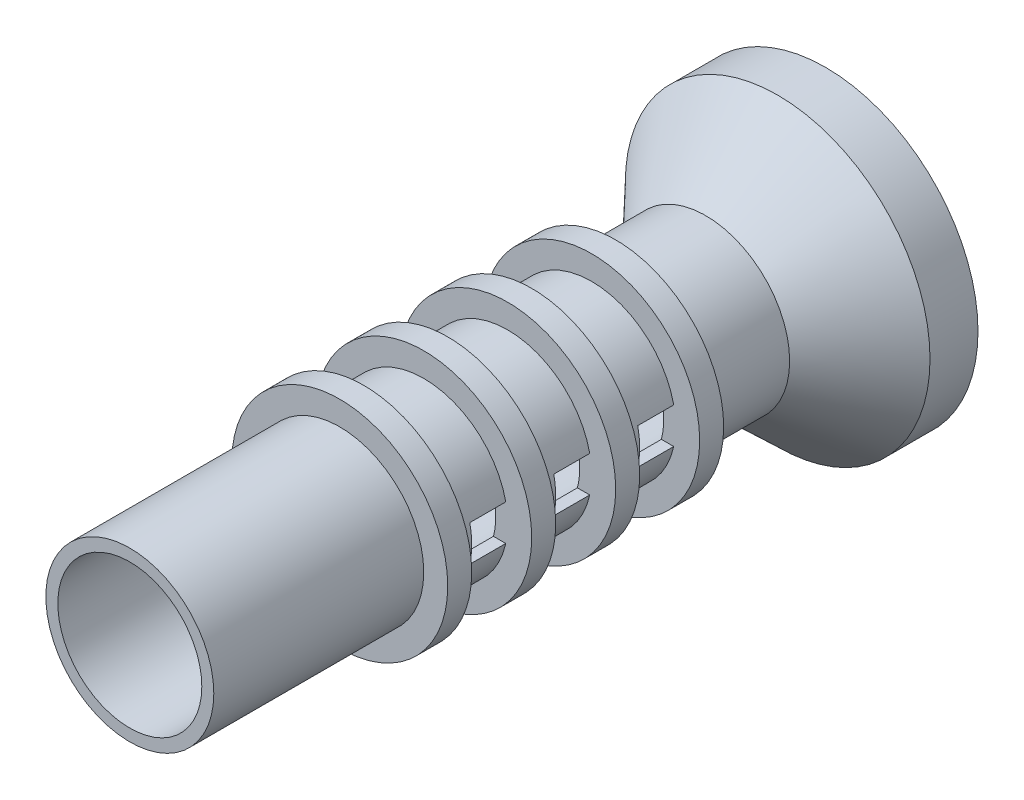
SolidWorks part; units mm, degrees
material "ABS"
ref_plane "正面" through (0, 0, 0) normal (0, 0, 1) x (1, 0, 0)
ref_plane "平面" through (0, 0, 0) normal (0, 1, 0) x (1, 0, 0)
ref_plane "右側面" through (0, 0, 0) normal (1, 0, 0) x (0, 0, -1)
sketch "ｽｹｯﾁ1" plane through (0, 0, 0) normal (0, 0, 1) x (1, 0, 0)
  circle A0 centre (0, 0) radius 3.5 construction
  circle A1 centre (0, 0) radius 6.35
  dimension "D1" = 7
  dimension "D2" = 12.7
ref_plane "平面1" through (0, 0, 5) normal (0, 0, 1) x (1, 0, 0)
sketch "ｽｹｯﾁ2" plane through (0, 0, 5) normal (0, 0, 1) x (1, 0, 0)
  circle A0 centre (0, 0) radius 3.5 construction
  circle A1 centre (0, 0) radius 3.5
ref_plane "平面2" through (0, 0, 29) normal (0, 0, 1) x (1, 0, 0)
ref_plane "平面3" through (0, 0, 24) normal (0, 0, 1) x (1, 0, 0)
sketch "ｽｹｯﾁ5" plane through (0, 0, 29) normal (0, 0, 1) x (1, 0, 0)
  circle A0 centre (0, 0) radius 6.35 construction
  circle A1 centre (0, 0) radius 6.35 construction
  circle A2 centre (0, 0) radius 3.5
  dimension "D1" = 7
extrude "ﾎﾞｽ - 押し出し3" add sketch "ｽｹｯﾁ2" along normal up to surface (19 mm away) contours A1 up to plane "平面3"
extrude "ﾎﾞｽ - 押し出し4" add sketch "ｽｹｯﾁ1" along normal blind 2 separate body
extrude "ﾎﾞｽ - 押し出し5" add sketch "ｽｹｯﾁ5" against normal blind 2
loft "ﾛﾌﾄ1" add section face at (6.35, 0, 2) section face at (3.5, 0, 5) connector at (-0.1759, 6.3476, 2) connector at (-0.0742, 3.4992, 5)
loft "ﾛﾌﾄ2" add section face at (3.5, 0, 24) section face at (3.5, 0, 27) connector at (-0.0749, 3.4992, 24) connector at (-0.0751, 3.4992, 27)
ref_plane "平面5" through (0, 0, 14.5) normal (0, 0, 1) x (1, 0, 0)
ref_plane "平面6" through (0, 0, 15.75) normal (0, 0, 1) x (1, 0, 0)
sketch "ｽｹｯﾁ9" plane through (0, 0, 15.75) normal (0, 0, 1) x (1, 0, 0)
  circle A0 centre (0, 0) radius 4.5
  dimension "D1" = 9
extrude "ﾎﾞｽ - 押し出し6" add sketch "ｽｹｯﾁ9" along normal blind 1
ref_plane "平面7" through (0, 0, 19.25) normal (0, 0, 1) x (1, 0, 0)
sketch "ｽｹｯﾁ10" plane through (0, 0, 19.25) normal (0, 0, 1) x (1, 0, 0)
  circle A1 centre (0, 0) radius 4.5
  circle A2 centre (0, 0) radius 4.5
  dimension "D1" = 0
extrude "ﾎﾞｽ - 押し出し7" add sketch "ｽｹｯﾁ10" along normal blind 1
mirror "ﾐﾗｰ3" about plane through (0, 0, 14.5) normal (0, 0, 1) of "ﾎﾞｽ - 押し出し7", "ﾎﾞｽ - 押し出し6"
sketch "ｽｹｯﾁ6" plane through (0, 0, 0) normal (0, 0, -1) x (-1, 0, 0)
  circle A0 centre (0, 0) radius 2.9
  dimension "D1" = 5.8
extrude "ｶｯﾄ - 押し出し1" cut sketch "ｽｹｯﾁ6" against normal blind 3
sketch "ｽｹｯﾁ7" plane through (0, 0, 3) normal (0, 0, -1) x (-1, 0, 0)
  circle A0 centre (0, 0) radius 1.8
  dimension "D1" = 3.6
extrude "ｶｯﾄ - 押し出し2" cut sketch "ｽｹｯﾁ7" against normal through all
sketch "ｽｹｯﾁ8" plane through (0, 0, 29) normal (0, 0, 1) x (1, 0, 0)
  circle A0 centre (0, 0) radius 3
  dimension "D1" = 6
extrude "ｶｯﾄ - 押し出し3" cut sketch "ｽｹｯﾁ8" against normal offset from surface (23 mm away) 3 up to face at (-1.8, 0, 3)
ref_plane "平面9" through (3.5, 0, 0) normal (1, 0, 0) x (0, 0, -1)
sketch "ｽｹｯﾁ11" plane through (3.5, 0, 0) normal (1, 0, 0) x (0, 0, -1)
  line L0 (0, 0) -> (-29, 0) construction
  line L1 (-29, 6.9851) -> (-29, -6.9851) construction
  line L2 (-16.75, 3.5) -> (-16.75, -3.5) construction
  line L3 (-18.25, 0.75) -> (-16.75, 0.75)
  line L4 (-18.25, 0.75) -> (-18.25, -0.75)
  line L5 (-18.25, -0.75) -> (-16.75, -0.75)
  line L6 (-16.75, 0.75) -> (-16.75, -0.75)
  line L7 (-18.25, 0.75) -> (-16.75, -0.75) construction
  line L8 (-18.25, -0.75) -> (-16.75, 0.75) construction
  line L9 (-13.25, 4.5) -> (-13.25, -4.5) construction
  line L10 (-14.75, 0.75) -> (-13.25, 0.75)
  line L11 (-14.75, 0.75) -> (-14.75, -0.75)
  line L12 (-14.75, -0.75) -> (-13.25, -0.75)
  line L13 (-13.25, 0.75) -> (-13.25, -0.75)
  line L14 (-14.75, 0.75) -> (-13.25, -0.75) construction
  line L15 (-14.75, -0.75) -> (-13.25, 0.75) construction
  line L16 (-9.75, 3.5) -> (-9.75, -3.5) construction
  line L17 (-11.25, 0.75) -> (-9.75, 0.75)
  line L18 (-11.25, 0.75) -> (-11.25, -0.75)
  line L19 (-11.25, -0.75) -> (-9.75, -0.75)
  line L20 (-9.75, 0.75) -> (-9.75, -0.75)
  line L21 (-11.25, 0.75) -> (-9.75, -0.75) construction
  line L22 (-11.25, -0.75) -> (-9.75, 0.75) construction
  point P5 (-17.5, 0)
  point P12 (-14, 0)
  point P19 (-10.5, 0)
  dimension "D1" = 1.5
  dimension "D2" = 1.5
extrude "ｶｯﾄ - 押し出し4" cut sketch "ｽｹｯﾁ11" against normal up to next
sketch "ｽｹｯﾁ12" plane through (0, 0, 0) normal (0, 0, -1) x (-1, 0, 0)
  line L0 (0, 0) -> (0, 2.9) construction
  line L1 (0, 0) -> (0.3949, 2.873) construction
  line L2 (0, 0) -> (0.7824, 2.7925) construction
  line L3 (0, 0) -> (1.1554, 2.6599) construction
  line L4 (0, 0) -> (1.5068, 2.4778) construction
  line L5 (0, 0) -> (1.8302, 2.2496) construction
  line L6 (0, 0) -> (2.1194, 1.9794) construction
  line L7 (0, 0) -> (2.3692, 1.6724) construction
  line L8 (0, 0) -> (2.5749, 1.3342) construction
  line L9 (0, 0) -> (2.7326, 0.9712) construction
  line L10 (0, 0) -> (2.8393, 0.59) construction
  line L11 (0, 0) -> (2.8932, 0.1979) construction
  line L12 (0, 0) -> (2.8932, -0.1979) construction
  line L13 (0, 0) -> (2.8393, -0.59) construction
  line L14 (0, 0) -> (2.7326, -0.9712) construction
  line L15 (0, 0) -> (2.5749, -1.3342) construction
  line L16 (0, 0) -> (2.3692, -1.6724) construction
  line L17 (0, 0) -> (2.1194, -1.9794) construction
  line L18 (0, 0) -> (1.8302, -2.2496) construction
  line L19 (0, 0) -> (1.5068, -2.4778) construction
  line L20 (0, 0) -> (1.1554, -2.6599) construction
  line L21 (0, 0) -> (0.7824, -2.7925) construction
  line L22 (0, 0) -> (0.3949, -2.873) construction
  line L23 (0, 0) -> (0, -2.9) construction
  line L24 (0, 0) -> (-0.3949, -2.873) construction
  line L25 (0, 0) -> (-0.7824, -2.7925) construction
  line L26 (0, 0) -> (-1.1554, -2.6599) construction
  line L27 (0, 0) -> (-1.5068, -2.4778) construction
  line L28 (0, 0) -> (-1.8302, -2.2496) construction
  line L29 (0, 0) -> (-2.1194, -1.9794) construction
  line L30 (0, 0) -> (-2.3692, -1.6724) construction
  line L31 (0, 0) -> (-2.5749, -1.3342) construction
  line L32 (0, 0) -> (-2.7326, -0.9712) construction
  line L33 (0, 0) -> (-2.8393, -0.59) construction
  line L34 (0, 0) -> (-2.8932, -0.1979) construction
  line L35 (0, 0) -> (-2.8932, 0.1979) construction
  line L36 (0, 0) -> (-2.8393, 0.59) construction
  line L37 (0, 0) -> (-2.7326, 0.9712) construction
  line L38 (0, 0) -> (-2.5749, 1.3342) construction
  line L39 (0, 0) -> (-2.3692, 1.6724) construction
  line L40 (0, 0) -> (-2.1194, 1.9794) construction
  line L41 (0, 0) -> (-1.8302, 2.2496) construction
  line L42 (0, 0) -> (-1.5068, 2.4778) construction
  line L43 (0, 0) -> (-1.1554, 2.6599) construction
  line L44 (0, 0) -> (-0.7824, 2.7925) construction
  line L45 (0, 0) -> (-0.3949, 2.873) construction
  line L46 (0, 0) -> (0.2081, 3.0429) construction
  line L47 (0.2081, 3.0429) -> (-0.066, 2.8992)
  line L48 (-0.066, 2.8992) -> (0, 0) construction
  line L49 (0, 0) -> (0.4602, 2.8633) construction
  line L50 (0.4602, 2.8633) -> (0.2081, 3.0429)
  line L51 (1.0214, 2.8739) -> (0.7186, 2.8095)
  line L52 (1.2156, 2.6329) -> (1.0214, 2.8739)
  line L53 (1.7589, 2.4918) -> (1.45, 2.5115)
  line L54 (1.8809, 2.2073) -> (1.7589, 2.4918)
  line L55 (2.3659, 1.9248) -> (2.0738, 2.0271)
  line L56 (2.4067, 1.618) -> (2.3659, 1.9248)
  line L57 (2.7975, 1.2151) -> (2.5438, 1.3925)
  line L58 (2.754, 0.9087) -> (2.7975, 1.2151)
  line L59 (3.0216, 0.4153) -> (2.8252, 0.6545)
  line L60 (2.897, 0.132) -> (3.0216, 0.4153)
  line L61 (3.0216, -0.4153) -> (2.897, -0.132)
  line L62 (2.8252, -0.6545) -> (3.0216, -0.4153)
  line L63 (2.7975, -1.2151) -> (2.754, -0.9087)
  line L64 (2.5438, -1.3925) -> (2.7975, -1.2151)
  line L65 (2.3659, -1.9248) -> (2.4067, -1.618)
  line L66 (2.0738, -2.0271) -> (2.3659, -1.9248)
  line L67 (1.7589, -2.4918) -> (1.8809, -2.2073)
  line L68 (1.45, -2.5115) -> (1.7589, -2.4918)
  line L69 (1.0214, -2.8739) -> (1.2156, -2.6329)
  line L70 (0.7186, -2.8095) -> (1.0214, -2.8739)
  line L71 (0.2081, -3.0429) -> (0.4602, -2.8633)
  line L72 (-0.066, -2.8992) -> (0.2081, -3.0429)
  line L73 (-0.6205, -2.9862) -> (-0.3294, -2.8812)
  line L74 (-0.8458, -2.7739) -> (-0.6205, -2.9862)
  line L75 (-1.4032, -2.708) -> (-1.0945, -2.6855)
  line L76 (-1.5628, -2.4429) -> (-1.4032, -2.708)
  line L77 (-2.0818, -2.229) -> (-1.7785, -2.2906)
  line L78 (-2.1639, -1.9306) -> (-2.0818, -2.229)
  line L79 (-2.606, -1.5847) -> (-2.3305, -1.7259)
  line L80 (-2.6046, -1.2752) -> (-2.606, -1.5847)
  line L81 (-2.9369, -0.8229) -> (-2.7097, -1.0331)
  line L82 (-2.852, -0.5252) -> (-2.9369, -0.8229)
  line L83 (-3.05, 0) -> (-2.888, -0.2637)
  line L84 (-2.888, 0.2637) -> (-3.05, 0)
  line L85 (-2.9369, 0.8229) -> (-2.852, 0.5252)
  line L86 (-2.7097, 1.0331) -> (-2.9369, 0.8229)
  line L87 (-2.606, 1.5847) -> (-2.6046, 1.2752)
  line L88 (-2.3305, 1.7259) -> (-2.606, 1.5847)
  line L89 (-2.0818, 2.229) -> (-2.1639, 1.9306)
  line L90 (-1.7785, 2.2906) -> (-2.0818, 2.229)
  line L91 (-1.4032, 2.708) -> (-1.5628, 2.4429)
  line L92 (-1.0945, 2.6855) -> (-1.4032, 2.708)
  line L93 (-0.6205, 2.9862) -> (-0.8458, 2.7739)
  line L94 (-0.3294, 2.8812) -> (-0.6205, 2.9862)
  circle A0 centre (0, 0) radius 2.9 construction
  circle A1 centre (0, 0) radius 3.05 construction
  arc A2 (0, 2.9) -> (0.3949, 2.873) centre (0, 0) cw construction
  circle A3 centre (0, 0) radius 2.9 construction
  arc A4 (-0.066, 2.8992) -> (0.4602, 2.8633) centre (0, 0) cw
  arc A5 (0.7186, 2.8095) -> (1.2156, 2.6329) centre (0, 0) cw
  arc A6 (1.45, 2.5115) -> (1.8809, 2.2073) centre (0, 0) cw
  arc A7 (2.0738, 2.0271) -> (2.4067, 1.618) centre (0, 0) cw
  arc A8 (2.5438, 1.3925) -> (2.754, 0.9087) centre (0, 0) cw
  arc A9 (2.8252, 0.6545) -> (2.897, 0.132) centre (0, 0) cw
  arc A10 (2.897, -0.132) -> (2.8252, -0.6545) centre (0, 0) cw
  arc A11 (2.754, -0.9087) -> (2.5438, -1.3925) centre (0, 0) cw
  arc A12 (2.4067, -1.618) -> (2.0738, -2.0271) centre (0, 0) cw
  arc A13 (1.8809, -2.2073) -> (1.45, -2.5115) centre (0, 0) cw
  arc A14 (1.2156, -2.6329) -> (0.7186, -2.8095) centre (0, 0) cw
  arc A15 (0.4602, -2.8633) -> (-0.066, -2.8992) centre (0, 0) cw
  arc A16 (-0.3294, -2.8812) -> (-0.8458, -2.7739) centre (0, 0) cw
  arc A17 (-1.0945, -2.6855) -> (-1.5628, -2.4429) centre (0, 0) cw
  arc A18 (-1.7785, -2.2906) -> (-2.1639, -1.9306) centre (0, 0) cw
  arc A19 (-2.3305, -1.7259) -> (-2.6046, -1.2752) centre (0, 0) cw
  arc A20 (-2.7097, -1.0331) -> (-2.852, -0.5252) centre (0, 0) cw
  arc A21 (-2.888, -0.2637) -> (-2.888, 0.2637) centre (0, 0) cw
  arc A22 (-2.852, 0.5252) -> (-2.7097, 1.0331) centre (0, 0) cw
  arc A23 (-2.6046, 1.2752) -> (-2.3305, 1.7259) centre (0, 0) cw
  arc A24 (-2.1639, 1.9306) -> (-1.7785, 2.2906) centre (0, 0) cw
  arc A25 (-1.5628, 2.4429) -> (-1.0945, 2.6855) centre (0, 0) cw
  arc A26 (-0.8458, 2.7739) -> (-0.3294, 2.8812) centre (0, 0) cw
  point P53 (0, 0)
  point P54 (0.1979, 2.8932)
  point P56 (0.1979, 2.8932)
  point P129 (0, 0)
  dimension "D2" = 6.1
  dimension "D3" = 10.435
  dimension "D1" = 46
  dimension "D4" = 23
extrude "ｶｯﾄ - 押し出し5" cut sketch "ｽｹｯﾁ12" against normal up to surface (3 mm away) up to face at (-1.8, 0, 3)
equation "\"D3@ｽｹｯﾁ12\"=360/23*2/3"
